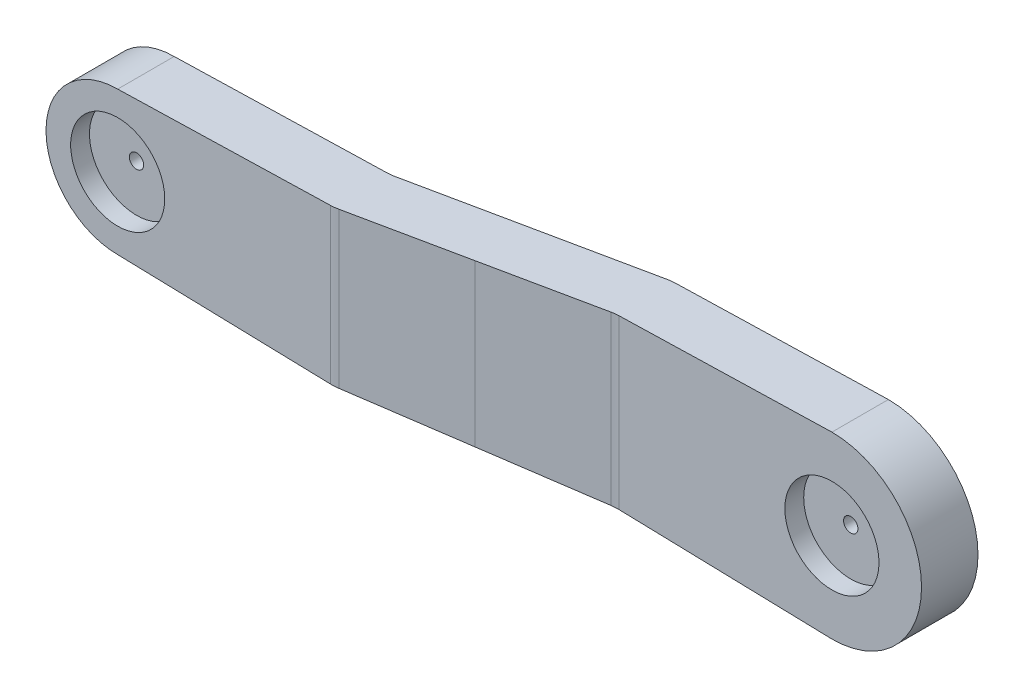
SolidWorks part; units mm, degrees
ref_plane "前视基准面" through (0, 0, 0) normal (0, 0, 1) x (1, 0, 0)
ref_plane "上视基准面" through (0, 0, 0) normal (0, 1, 0) x (1, 0, 0)
ref_plane "右视基准面" through (0, 0, 0) normal (1, 0, 0) x (0, 0, -1)
other "Configuration Table"
sketch "草图1" plane through (0, 0, 0) normal (0, 0, 1) x (1, 0, 0)
  line L0 (0, 16) -> (150, 20)
  line L1 (150, -20) -> (0, -16)
  arc A0 (0, 16) -> (0, -16) centre (0, 0) ccw
  arc A1 (150, -20) -> (150, 20) centre (150, 0) ccw
  dimension "D2" = 32
  dimension "D3" = 40
  dimension "D1" = 150
extrude "凸台-拉伸1" add sketch "草图1" along normal blind 22
sketch "草图2" plane through (0, 0, 22) normal (0, 0, 1) x (1, 0, 0)
  circle A0 centre (0, 0) radius 10.5
  dimension "D1" = 21
extrude "切除-拉伸1" cut sketch "草图2" against normal blind 4.2
sketch "草图9" plane through (0, 0, 22) normal (0, 0, 1) x (1, 0, 0)
  line L0 (75, 18) -> (75, -18)
  line L1 (150, 20) -> (0, 16) construction
  line L2 (0, -16) -> (150, -20) construction
  line L5 (0, -16) -> (150, -20)
  line L6 (150, 20) -> (0, 16)
  line L7 (75, -18) -> (150, -20)
  line L8 (150, 20) -> (75, 18)
  arc A2 (0, 16) -> (0, -16) centre (0, 0) ccw
  arc A3 (150, -20) -> (150, 20) centre (150, 0) ccw
  arc A5 (150, -20) -> (150, 20) centre (150, 0) ccw
  dimension "D1" = 0
extrude "切除-拉伸6" cut sketch "草图9" against normal blind 9.4
sketch "草图10" plane through (0, 0, 0) normal (0, 0, -1) x (-1, 0, 0)
  line L0 (-75, 18) -> (-75, -18)
  line L1 (-150, 20) -> (0, 16) construction
  line L2 (0, -16) -> (-150, -20) construction
  line L5 (0, 16) -> (-150, 20)
  line L6 (-150, -20) -> (0, -16)
  line L7 (0, 16) -> (-75, 18)
  line L8 (-75, -18) -> (0, -16)
  arc A2 (0, -16) -> (0, 16) centre (0, 0) ccw
  arc A3 (-150, 20) -> (-150, -20) centre (-150, 0) ccw
  arc A4 (0, -16) -> (0, 16) centre (0, 0) ccw
  dimension "D1" = 0
extrude "切除-拉伸7" cut sketch "草图10" against normal blind 9.4
sketch "草图4" plane through (0, 0, 12.6) normal (0, 0, -1) x (-1, 0, 0)
  circle A0 centre (-150, 0) radius 10.5
  arc A2 (-150, 20) -> (-150, -20) centre (-150, 0) ccw construction
  dimension "D1" = 21
extrude "切除-拉伸2" cut sketch "草图4" along normal blind 4.2
sketch "草图8" plane through (0, 0, 17.8) normal (0, 0, 1) x (1, 0, 0)
  circle A0 centre (0, 0) radius 1.6
  circle A1 centre (150, 0) radius 1.6
  dimension "D1" = 3.2
  dimension "D2" = 3.2
extrude "切除-拉伸5" cut sketch "草图8" against normal through all
chamfer "倒角1" distance 4.7 angle 80 2 edges at (75, 0, 12.6) (75, 0, 9.4) first distance on face at (75, 0, 17.3) first distance on face at (75, 0, 4.7)
chamfer "倒角2" distance 4.7 angle 80 1 edges at (75, 0, 22) first distance on face at (75, 0, 19.65)
chamfer "倒角3" distance 4.7 angle 80 1 edges at (75, 0, 0) first distance on face at (75, 0, 2.35)
ref_plane "基准面1" through (100, 0, 0) normal (1, 0, 0) x (0, 0, -1)
sketch "草图5" plane through (100, 0, 0) normal (1, 0, 0) x (0, 0, -1)
  line L2 (0, -1.6) -> (0, 1.6) construction
  line L3 (0, 10) -> (0, 8)
  line L4 (0, -8) -> (0, -10)
  arc A0 (0, 8) -> (0, -8) centre (0, 0) cw
  arc A1 (0, 10) -> (0, -10) centre (0, 0) cw
  dimension "D1" = 8
  dimension "D2" = 2
extrude "凸台-拉伸2" [suppressed] add sketch "草图5" along normal blind 30 and the other way blind 30
sketch "草图6" [suppressed] plane through (130, 0, 0) normal (1, 0, 0) x (0, 0, -1)
  line L0 (0, -16) -> (0, 16) construction
  line L1 (0, 8) -> (0, -8)
  arc A0 (0, 8) -> (0, -8) centre (0, 0) ccw
  arc A1 (0, -8) -> (0, 8) centre (0, 0) ccw construction
extrude "切除-拉伸3" [suppressed] cut sketch "草图6" against normal offset from surface 10 and the other way blind 10 offset beyond the face yes
sketch "草图7" [suppressed] plane through (0, 0, 0) normal (0, 0, -1) x (-1, 0, 0)
  line L0 (-134, 6) -> (-126, 6)
  line L2 (-126, 6) -> (-126, -6)
  line L3 (-126, -6) -> (-134, -6)
  line L5 (-134, -6) -> (-134, 6)
  line L6 (-130, 10) -> (-130, 8) construction
  line L7 (-100, 17.6) -> (-100, -17.6) construction
  line L8 (-74, -6) -> (-66, -6)
  line L9 (-66, 6) -> (-74, 6)
  line L10 (-74, 6) -> (-74, -6)
  line L11 (-66, -6) -> (-66, 6)
  line L12 (-145.6282, 0) -> (-50.8938, 0) construction
  point P5 (-130, 6)
  point P8 (-134, 0)
  dimension "D1" = 8
  dimension "D2" = 12
extrude "切除-拉伸4" [suppressed] cut sketch "草图7" against normal through all
fillet "圆角1" [suppressed] radius 5
fillet "圆角2" [suppressed] radius 2
fillet "圆角3" [suppressed] radius 2
fillet "圆角4" radius 10 4 edges at (48.345, 0, 9.4) (101.655, 0, 0) (101.655, 0, 12.6) (48.345, 0, 22)
